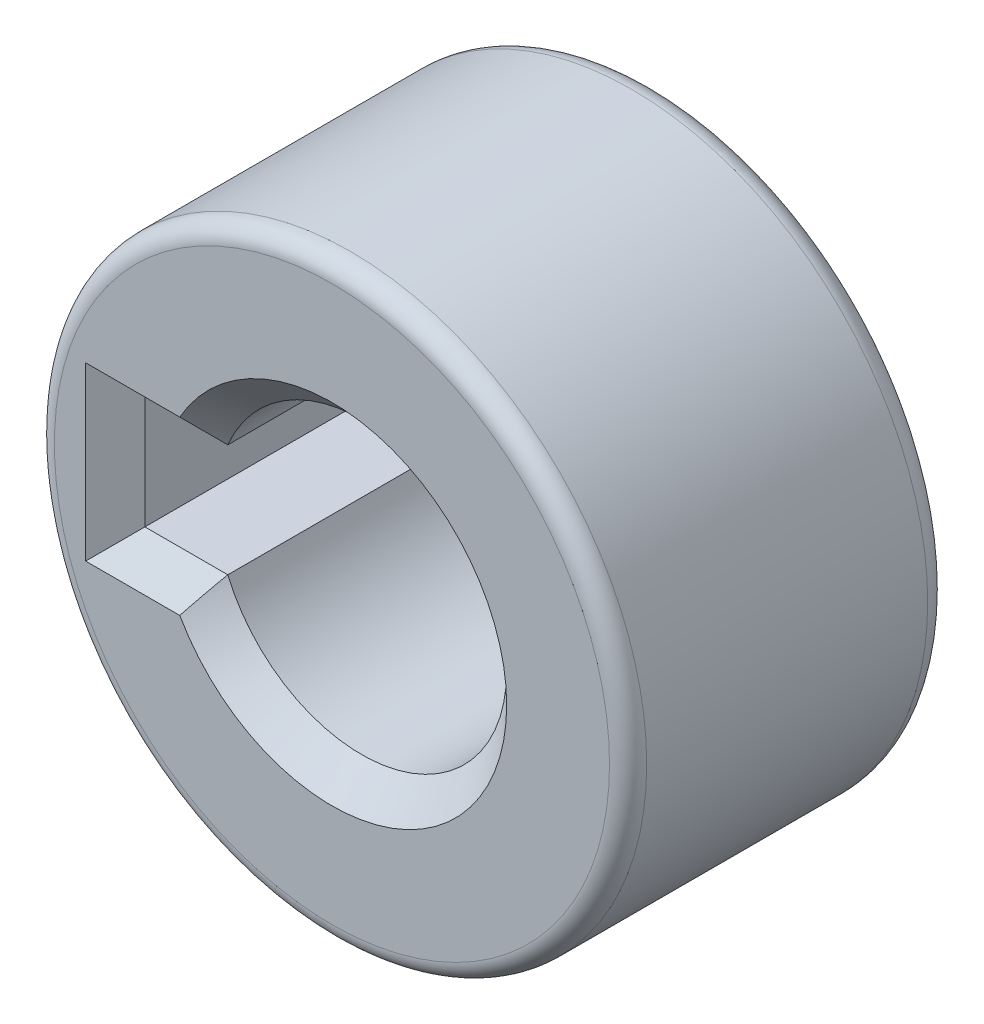
SolidWorks part; units mm, degrees
ref_plane "Front Plane" through (0, 0, 0) normal (1, 0, 0) x (0, 1, 0)
ref_plane "Top Plane" through (0, 0, 0) normal (0, 0, 1) x (0, 1, 0)
ref_plane "Right Plane" through (0, 0, 0) normal (0, 1, 0) x (-1, 0, 0)
sketch "Sketch1" plane through (0, 0, 0) normal (0, 0, 1) x (0, 1, 0)
  circle A0 centre (0, 0) radius 10
  dimension "D1" = 20
extrude "Boss-Extrude1" add sketch "Sketch1" along normal blind 10.9
sketch "Sketch2" plane through (0, 0, 10.9) normal (0, 0, 1) x (1, 0, 0)
  line L1 (-7.3166, 1.9) -> (-3.7207, 1.9)
  line L2 (-7.3166, 1.9) -> (-7.3166, -1.9)
  line L3 (-7.3166, -1.9) -> (-3.7207, -1.9)
  line L4 (-3.7207, 1.9) -> (-3.7207, -1.9)
  circle A0 centre (0, 0) radius 4.9
  point P7 (-7.3166, 0)
  point P8 (-4.5166, 1.9)
  point P9 (0, 0)
  dimension "D1" = 9.8
  dimension "D3" = 2.8
  dimension "D2" = 3.8
extrude "Cut-Extrude1" cut sketch "Sketch2" against normal blind 10 and the other way blind 10 contours L3 A0 L1 L4 | L2 L1 L4 L3 region at (0.2384, 0, 10.9)
chamfer "Chamfer1" distance 1 angle 45 4 edges at (-5.9166, -1.9, 10.9) (-7.3166, 0, 10.9) (-5.9166, 1.9, 10.9) (4.9, 0, 10.9)
scale "Scale1" scale about centroid uniform scaling yes scale factor 0.75
scale "Scale2" scale about centroid uniform scaling yes scale factor 0.85
fillet "Fillet1" radius 0.4 1 edges at (6.4612, 0, 8.856)
fillet "Fillet2" radius 0.5 1 edges at (6.4612, 0, 1.9073)
